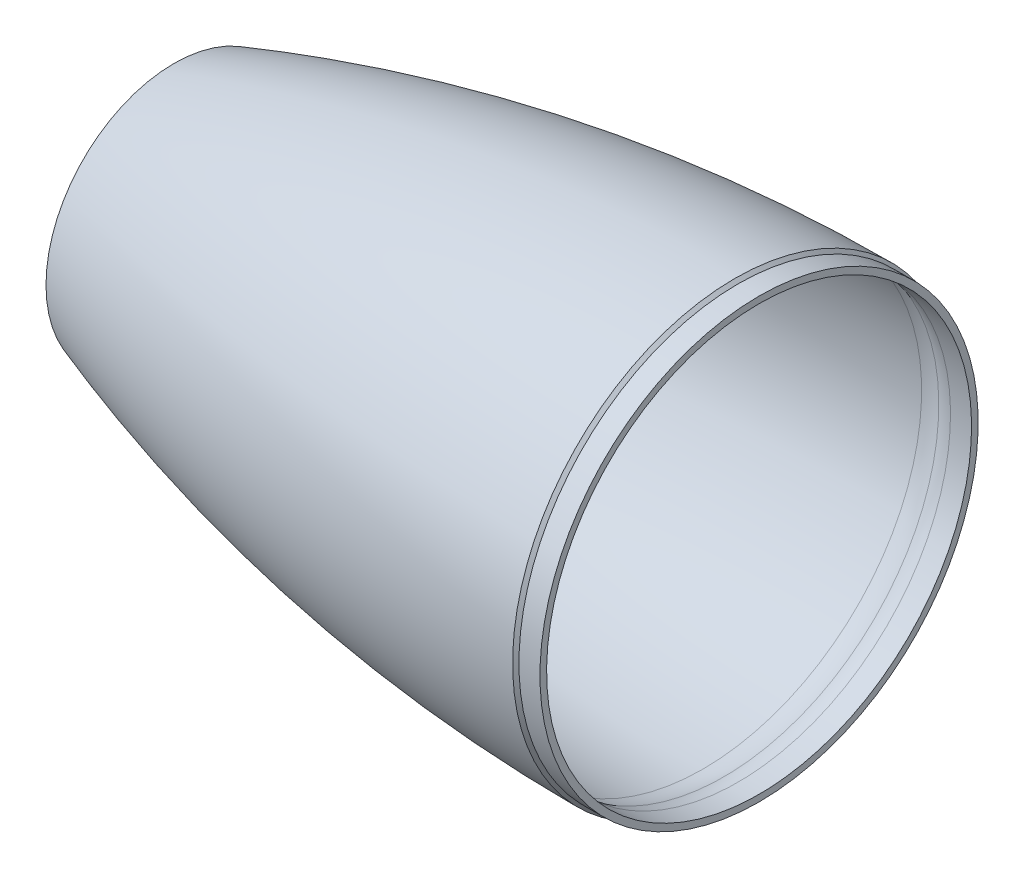
SolidWorks part; units mm, degrees
ref_plane "Front Plane" through (0, 0, 0) normal (0, 0, 1) x (1, 0, 0)
ref_plane "Top Plane" through (0, 0, 0) normal (0, 1, 0) x (1, 0, 0)
ref_plane "Right Plane" through (0, 0, 0) normal (1, 0, 0) x (0, 0, -1)
sketch "Sketch1" plane through (0, 0, 0) normal (0, 0, 1) x (1, 0, 0)
  line L4 (0, 0) -> (-304.8, 0) construction
  line L9 (0, 76.975) -> (0, 0) construction
  line L10 (0, 80.518) -> (50.8, 80.518) construction
  line L11 (-203.2, 46.355) -> (-203.2, 41.4909)
  line L12 (-203.2, 41.4909) -> (-197.8912, 41.4909)
  line L14 (-193.8095, 42.9765) -> (-184.6287, 50.6802)
  line L15 (1.143, 79.375) -> (8.763, 79.375)
  line L16 (0, 80.518) -> (1.143, 79.375)
  line L17 (1.143, 76.975) -> (8.763, 76.975)
  line L18 (8.763, 76.975) -> (8.763, 79.375)
  arc A4 (0, 80.518) -> (-203.2, 46.355) centre (0, -540.8758) ccw
  arc A5 (-11.557, 79.2103) -> (-182.4147, 51.8849) centre (0, -540.8758) ccw
  arc A6 (0, 79.318) -> (-202.8076, 45.221) centre (0, -540.8758) ccw construction
  arc A10 (-4.0446, 77.9175) -> (1.143, 76.975) centre (1.143, 91.722) ccw
  arc A11 (-197.8912, 41.4909) -> (-193.8095, 42.9765) centre (-197.8912, 47.8409) ccw
  arc A12 (-182.4147, 51.8849) -> (-184.6287, 50.6802) centre (-180.547, 45.8158) ccw
  arc A13 (-11.557, 79.2103) -> (-4.0446, 77.9175) centre (-11.1791, 58.9324) cw
  point P6 (-2.0581, 77.6809)
  point P8 (-57.2734, -19.8104)
  point P9 (0, 313.4439)
  point P10 (-150.9565, 274.6984)
  point P21 (-195.58, 41.4909)
  dimension "D7" = 7.62
  dimension "D10" = 6.35
  dimension "D17" = 5.1876
  dimension "D8" = 140
  dimension "D16" = 12.7
  dimension "D1" = 161.036
  dimension "D2" = 50.8
  dimension "D3" = 203.2
  dimension "D4" = 92.71
  dimension "D6" = 82.9818
  dimension "D9" = 304.8
  dimension "D12" = 7.62
  dimension "D13" = 158.75
  dimension "D14" = 45
  dimension "D15" = 2.4
  dimension "D5" = 1.2
revolve "Revolve1" add sketch "Sketch1" angle 360 about L4
